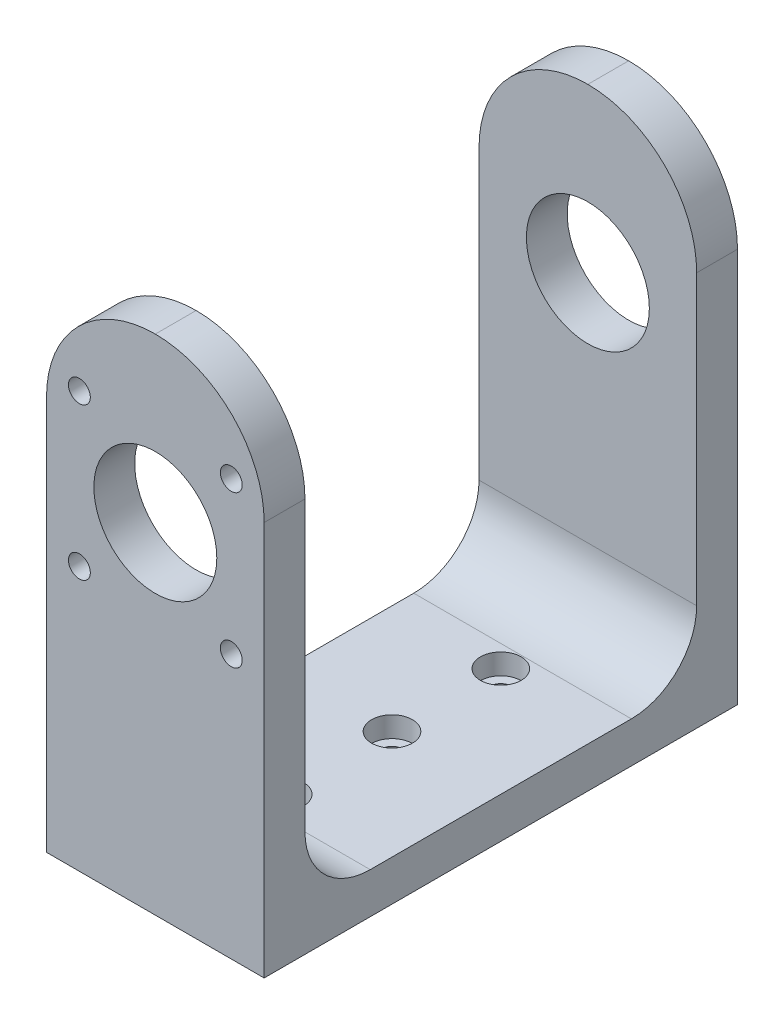
SolidWorks part; units mm, degrees
ref_plane "Front Plane" through (0, 0, 0) normal (0, 0, 1) x (1, 0, 0)
ref_plane "Top Plane" through (0, 0, 0) normal (0, 1, 0) x (1, 0, 0)
ref_plane "Right Plane" through (0, 0, 0) normal (1, 0, 0) x (0, 0, -1)
sketch "Sketch1" plane through (0, 0, 0) normal (0, 1, 0) x (1, 0, 0)
  line L1 (0, 0) -> (50.8, 0)
  line L2 (0, 0) -> (0, 110.49)
  line L3 (0, 110.49) -> (50.8, 110.49)
  line L4 (50.8, 0) -> (50.8, 110.49)
  dimension "D1" = 50.8
  dimension "D2" = 110.49
extrude "Boss-Extrude1" add sketch "Sketch1" along normal blind 9.525 contours L2 L1 L4 L3
sketch "Sketch2" plane through (0, 9.525, 0) normal (0, 1, 0) x (1, 0, 0)
  line L0 (0, 0) -> (0, 110.49) construction
  line L1 (50.8, 110.49) -> (0, 110.49)
  line L2 (50.8, 110.49) -> (50.8, 100.965)
  line L3 (50.8, 100.965) -> (0, 100.965)
  line L4 (0, 110.49) -> (0, 100.965)
  dimension "D1" = 9.525
extrude "Boss-Extrude2" add sketch "Sketch2" along normal blind 107.95 contours L2 L1 L4 L3
sketch "Sketch3" plane through (0, 9.525, 0) normal (0, 1, 0) x (1, 0, 0)
  line L0 (50.8, 0) -> (50.8, 100.965) construction
  line L1 (0, 0) -> (50.8, 0)
  line L2 (0, 0) -> (0, 9.525)
  line L3 (0, 9.525) -> (50.8, 9.525)
  line L4 (50.8, 0) -> (50.8, 9.525)
  dimension "D1" = 9.525
extrude "Boss-Extrude3" add sketch "Sketch3" along normal blind 107.95
sketch "Sketch8" plane through (0, 0, 0) normal (0, 0, 1) x (1, 0, 0)
  line L0 (0, 117.475) -> (50.8, 117.475) construction
  circle A0 centre (25.4, 79.375) radius 14.351
  dimension "D1" = 28.702
  dimension "D2" = 38.1
extrude "Cut-Extrude7" cut sketch "Sketch8" against normal through all contours A0
sketch "Sketch9" plane through (0, 0, -9.525) normal (0, 0, -1) x (-1, 0, 0)
  line L0 (-43.1292, 97.1042) -> (-7.6708, 61.6458) construction
  circle A0 centre (-43.1292, 97.1042) radius 2.5527
  circle A1 centre (-7.6708, 97.1042) radius 2.5527
  circle A2 centre (-7.6708, 61.6458) radius 2.5527
  circle A3 centre (-43.1292, 61.6458) radius 2.5527
  circle A4 centre (-25.4, 79.375) radius 14.351 construction
  point P2 (0, 0)
  point P11 (0, 0)
  point P12 (0, 0)
  dimension "D1" = 35.4584
  dimension "D2" = 35.4584
  dimension "D3" = 35.4584
  dimension "D4" = 5.1054
  dimension "D5" = 17.7292
  dimension "D6" = 17.7292
extrude "Cut-Extrude8" cut sketch "Sketch9" against normal through all
sketch "Sketch10" plane through (0, 0, -110.49) normal (0, 0, -1) x (-1, 0, 0)
  circle A0 centre (-43.1292, 97.1042) radius 2.5527
  circle A1 centre (-7.6708, 97.1042) radius 2.5527
  circle A2 centre (-7.6708, 61.6458) radius 2.5527
  circle A3 centre (-43.1292, 61.6458) radius 2.5527
  circle A4 centre (-7.6708, 61.6458) radius 2.5527 construction
  circle A5 centre (-7.6708, 97.1042) radius 2.5527 construction
  circle A6 centre (-43.1292, 61.6458) radius 2.5527 construction
  circle A7 centre (-43.1292, 97.1042) radius 2.5527 construction
  point P0 (0, 0)
  dimension "D1" = 5.1054
extrude "Cut-Extrude9" cut sketch "Sketch10" against normal blind 6.35
fillet "Fillet5" radius 25.4 1 edges at (0, 117.475, -4.7625)
fillet "Fillet6" radius 25.4 1 edges at (50.8, 117.475, -4.7625)
fillet "Fillet7" radius 25.4 1 edges at (0, 117.475, -105.7275)
fillet "Fillet8" radius 25.4 1 edges at (50.8, 117.475, -105.7275)
sketch "Sketch11" plane through (0, 9.525, 0) normal (0, 1, 0) x (1, 0, 0)
  line L1 (50.8, 9.525) -> (50.8, 100.965) construction
  line L2 (50.8, 100.965) -> (0, 100.965) construction
  circle A0 centre (25.4, 55.245) radius 2.5527
  point P2 (0, 0)
  point P3 (0, 0)
  point P5 (0, 0)
  point P6 (0, 0)
  point P7 (34.4737, 36.6434)
  point P9 (50.8, 55.245)
  point P12 (25.4, 100.965)
  dimension "D1" = 5.1054
  dimension "D2" = 0
  dimension "D3" = 0
extrude "Cut-Extrude10" cut sketch "Sketch11" against normal through all
sketch "Sketch12" plane through (0, 9.525, 0) normal (0, 1, 0) x (1, 0, 0)
  circle A0 centre (25.4, 29.845) radius 2.54
  circle A1 centre (25.4, 55.245) radius 2.5527 construction
  circle A2 centre (25.4, 80.645) radius 2.54
  dimension "D1" = 25.4
  dimension "D2" = 25.4
extrude "Cut-Extrude11" cut sketch "Sketch12" against normal through all
fillet "Fillet9" radius 15.24 2 edges at (25.4, 9.525, -9.525) (25.4, 9.525, -100.965)
sketch "Sketch13" plane through (0, 9.525, 0) normal (0, 1, 0) x (1, 0, 0)
  circle A0 centre (25.4, 55.245) radius 4.7625
  circle A1 centre (25.4, 29.845) radius 4.7625
  circle A3 centre (25.4, 80.645) radius 4.7625
  dimension "D1" = 9.525
extrude "Cut-Extrude12" cut sketch "Sketch13" against normal blind 4.826
